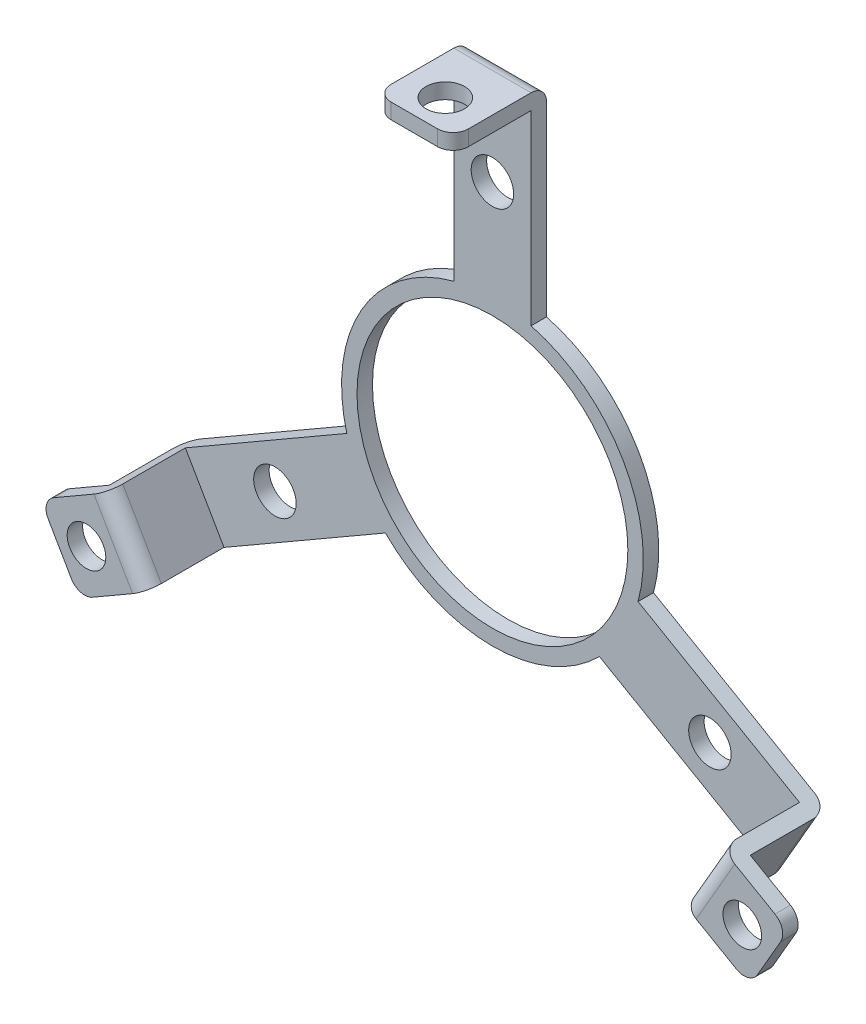
SolidWorks part; units mm, degrees
material "AISI 1020"
ref_plane "Front Plane" through (0, 0, 0) normal (0, 0, 1) x (1, 0, 0)
ref_plane "Top Plane" through (0, 0, 0) normal (0, 1, 0) x (1, 0, 0)
ref_plane "Right Plane" through (0, 0, 0) normal (1, 0, 0) x (0, 0, -1)
sketch "Sketch1" plane through (0, 0, 0) normal (0, 0, 1) x (1, 0, 0)
  line L12 (0, 53.5743) -> (0, -53.5743) construction
  line L13 (0, 0) -> (-54.3216, -31.3626) construction
  line L14 (0, 0) -> (59.2688, -34.2189) construction
  line L15 (-47.3993, -23.9019) -> (-44.3993, -29.0981)
  line L16 (-41.6673, -29.8301) -> (-36.4711, -26.8301)
  line L17 (-36.4711, -26.8301) -> (-41.4711, -18.1699)
  line L18 (-41.4711, -18.1699) -> (-46.6673, -21.1699)
  line L19 (-42.4352, -24.5) -> (-47.3305, -16.0211) construction
  line L20 (41.6673, -29.8301) -> (36.4711, -26.8301)
  line L21 (47.3993, -23.9019) -> (44.3993, -29.0981)
  line L22 (41.4711, -18.1699) -> (46.6673, -21.1699)
  line L23 (36.4711, -26.8301) -> (41.4711, -18.1699)
  circle A1 centre (-42.4352, -24.5) radius 2.5
  circle A2 centre (42.4352, -24.5) radius 2.5
  arc A3 (41.6673, -29.8301) -> (44.3993, -29.0981) centre (42.6673, -28.0981) ccw
  arc A4 (47.3993, -23.9019) -> (46.6673, -21.1699) centre (45.6673, -22.9019) ccw
  arc A5 (-47.3993, -23.9019) -> (-46.6673, -21.1699) centre (-45.6673, -22.9019) cw
  arc A6 (-44.3993, -29.0981) -> (-41.6673, -29.8301) centre (-42.6673, -28.0981) ccw
  point P29 (43.3993, -30.8301)
  point P32 (48.3993, -22.1699)
  point P35 (-48.3993, -22.1699)
  point P38 (-43.3993, -30.8301)
  dimension "D9" = 5
  dimension "D10" = 5
  dimension "D15" = 2
  dimension "D1" = 120
  dimension "D2" = 120
  dimension "D11" = 49
  dimension "D12" = 49
  dimension "D13" = 10
  dimension "D14" = 8
extrude "Boss-Extrude1" add sketch "Sketch1" along normal blind 2
ref_plane "Plane1" through (0, 0, 2) normal (0, 0, 1) x (1, 0, 0)
sketch "Sketch2" plane through (0, 0, 2) normal (0, 0, 1) x (1, 0, 0)
  line L0 (-41.4711, -18.1699) -> (-36.4711, -26.8301)
  line L1 (-5, 45) -> (5, 45)
  line L2 (-5, 45) -> (-5, 43)
  line L3 (-5, 43) -> (5, 43)
  line L4 (5, 45) -> (5, 43)
  line L5 (-36.4711, -26.8301) -> (-34.7391, -25.8301)
  line L6 (-34.7391, -25.8301) -> (-39.7391, -17.1699)
  line L7 (-39.7391, -17.1699) -> (-41.4711, -18.1699)
  line L8 (36.4711, -26.8301) -> (34.7391, -25.8301)
  line L9 (34.7391, -25.8301) -> (39.7391, -17.1699)
  line L10 (39.7391, -17.1699) -> (41.4711, -18.1699)
  line L11 (41.4711, -18.1699) -> (36.4711, -26.8301) construction
  line L12 (41.4711, -18.1699) -> (36.4711, -26.8301)
  dimension "D1" = 10
  dimension "D2" = 2
  dimension "D3" = 2
  dimension "D4" = 2
  dimension "D5" = 10
extrude "Boss-Extrude2" add sketch "Sketch2" against normal blind 10.1 contours L12 L10 L9 L8 | L6 L7 L0 L5 region at (-38.1051, -22, 2) region at (38.1051, -22, 2)
ref_plane "Plane2" through (0, 0, -8.1) normal (0, 0, -1) x (-1, 0, 0)
sketch "Sketch3" plane through (0, 0, -8.1) normal (0, 0, -1) x (-1, 0, 0)
  line L0 (-41.4711, -18.1699) -> (-36.4711, -26.8301)
  line L1 (-5, 45) -> (5, 45)
  line L2 (-5, 45) -> (-5, 18.8739)
  line L4 (5, 45) -> (5, 18.8739)
  line L5 (-36.4711, -26.8301) -> (-13.8453, -13.7671)
  line L6 (-41.4711, -18.1699) -> (-18.8453, -5.1068)
  line L7 (41.4711, -18.1699) -> (36.4711, -26.8301)
  line L8 (36.4711, -26.8301) -> (13.8453, -13.7671)
  line L9 (41.4711, -18.1699) -> (18.8453, -5.1068)
  circle A0 centre (0, 0) radius 17.525
  arc A1 (-5, 18.8739) -> (-18.8453, -5.1068) centre (0, 0) ccw
  arc A2 (-13.8453, -13.7671) -> (13.8453, -13.7671) centre (0, 0) ccw
  arc A3 (18.8453, -5.1068) -> (5, 18.8739) centre (0, 0) ccw
  dimension "D1" = 35.05
  dimension "D2" = 2
extrude "Boss-Extrude3" add sketch "Sketch3" along normal blind 2
sketch "Sketch4" plane through (0, 0, -8.1) normal (0, 0, 1) x (1, 0, 0)
  line L0 (-5, 18.8739) -> (-5, 45) construction
  circle A0 centre (0, 32.5) radius 2.75
  dimension "D2" = 5.5
  dimension "D1" = 32.5
  dimension "D3" = 5
extrude "Cut-Extrude1" cut sketch "Sketch4" against normal through all
extrude "Boss-Extrude4" add sketch "Sketch2<3>" against normal up to surface (12.1 mm away) contours L4 L1 L2 L3 region at (0, 44, 2) up to face at (2.75, 32.5, -10.1)
sketch "Sketch2<3>" plane through (0, 0, 2) normal (0, 0, 1) x (1, 0, 0) same geometry as "Sketch2"
ref_plane "Plane3" through (0, 43, 0) normal (0, -1, 0) x (-1, 0, 0)
sketch "Sketch5" plane through (0, 45, 0) normal (0, 1, 0) x (1, 0, 0)
  line L0 (-5, -2) -> (5, -2) construction
  circle A0 centre (0, 2) radius 2.5
  dimension "D1" = 5
  dimension "D2" = 4
extrude "Cut-Extrude2" cut sketch "Sketch5" against normal up to next
fillet "Fillet2" radius 2 7 edges at (5, 44, 2) (-5, 44, 2) (37.2391, -21.5, 2) (-37.2391, -21.5, 2) (-38.9711, -22.5, -10.1) (38.9711, -22.5, -10.1) (0, 45, -10.1)
sketch "Sketch6" plane through (0, 0, -8.1) normal (0, 0, 1) x (1, 0, 0)
  circle A2 centre (0, 32.5) radius 2.75 construction
  circle A3 centre (0, 32.5) radius 2.75
  circle A4 centre (28.1458, -16.25) radius 2.75
  circle A5 centre (-28.1458, -16.25) radius 2.75
  point P6 (0, 0)
  point P11 (0, 0)
  dimension "D1" = 3
extrude "Cut-Extrude3" cut sketch "Sketch6" against normal blind 10
